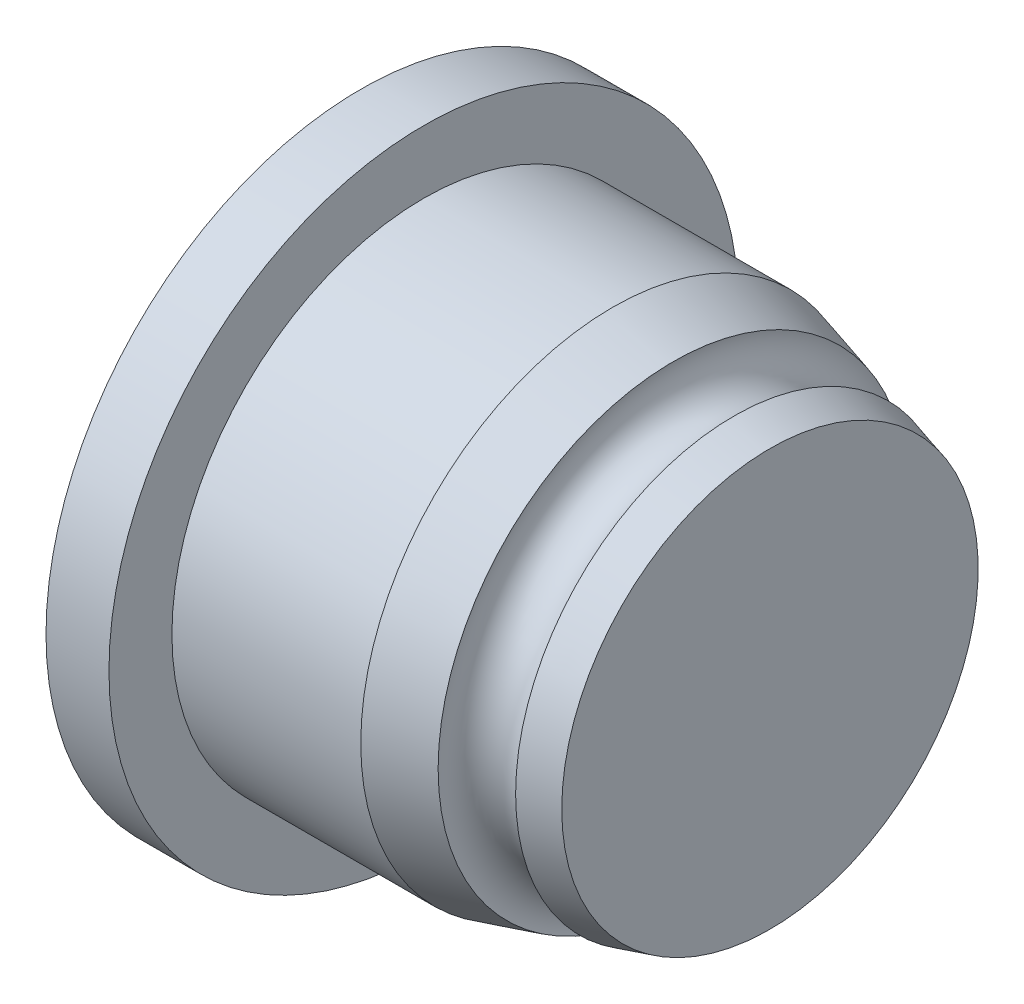
SolidWorks part; units mm, degrees
ref_plane "Front Plane" through (0, 0, 0) normal (0, 0, 1) x (1, 0, 0)
ref_plane "Top Plane" through (0, 0, 0) normal (0, 1, 0) x (1, 0, 0)
ref_plane "Right Plane" through (0, 0, 0) normal (1, 0, 0) x (0, 0, -1)
other "Configuration Table"
sketch "Sketch2" plane through (0, 0, 0) normal (0, 1, 0) x (1, 0, 0)
  line L0 (0, 0) -> (0, 5)
  line L1 (0, 5) -> (1, 5)
  line L2 (1, 5) -> (1, 4)
  line L3 (1, 4) -> (4, 4)
  line L4 (0, 0) -> (6.5, 0)
  line L5 (6.5, 0) -> (6.5, 3.3075)
  line L7 (4, 4) -> (6.5, 3.3075) construction
  line L8 (4, 4) -> (4.9622, 3.7335)
  line L9 (5.926, 3.4665) -> (6.5, 3.3075)
  arc A0 (4.9622, 3.7335) -> (5.926, 3.4665) centre (5.4441, 3.6) ccw
  dimension "D1" = 3
  dimension "D4" = 3.6
  dimension "D2" = 5
  dimension "D3" = 4
  dimension "D5" = 2.5
revolve "Revolve1" add sketch "Sketch2" angle 360 about L4
sketch "Sketch3" plane through (0, 0, 0) normal (-1, 0, 0) x (0, 0, 1)
  circle A0 centre (0, 0) radius 1.75
extrude "Boss-Extrude1" add sketch "Sketch3" against normal blind 4
sketch "Sketch4" plane through (0, 0, 0) normal (-1, 0, 0) x (0, 0, 1)
  circle A0 centre (0, 0) radius 2.4
extrude "Cut-Extrude1" cut sketch "Sketch4" against normal blind 5 and the other way through all
